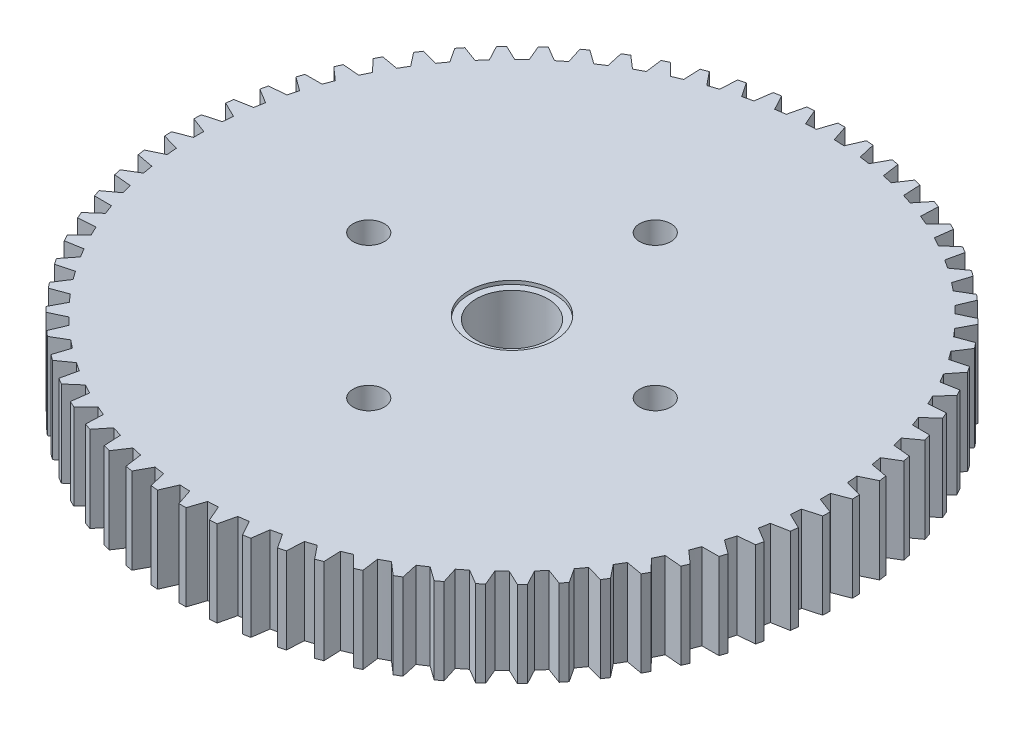
SolidWorks part; units mm, degrees
material "ABS"
ref_plane "Front" through (0, 0, 0) normal (0, 0, 1) x (1, 0, 0)
ref_plane "Top" through (0, 0, 0) normal (0, 1, 0) x (1, 0, 0)
ref_plane "Right" through (0, 0, 0) normal (1, 0, 0) x (0, 0, -1)
sketch "Sketch2" plane through (0, 0, 0) normal (0, 1, 0) x (1, 0, 0)
  circle A0 centre (0, 0) radius 21.875
  circle A1 centre (0, 0) radius 2.5
  dimension "D1" = 43.75
  dimension "D2" = 5
extrude "Boss-Extrude1" add sketch "Sketch2" along normal blind 6
ref_plane "Plane1" through (0, 3.5, 0) normal (0, 1, 0) x (1, 0, 0)
sketch "Sketch3" plane through (0, 3.5, 0) normal (0, 1, 0) x (1, 0, 0)
  line L0 (0, 21.875) -> (0, -21.875) construction
  line L1 (-21.875, 0) -> (21.875, 0) construction
  line L3 (0, 21.875) -> (0, 23) construction
  line L4 (-0.625, 21.8661) -> (-0.25, 23)
  line L5 (-0.25, 23) -> (0.25, 23)
  line L6 (0.625, 21.8661) -> (0.25, 23)
  circle A0 centre (0, 0) radius 21.875 construction
  arc A1 (-21.875, 0) -> (21.875, 0) centre (0, 0) ccw
  arc A2 (0.625, 21.8661) -> (-0.625, 21.8661) centre (0, 0) ccw
  dimension "D1" = 1.25
  dimension "D2" = 0.25
  dimension "D3" = 23
extrude "Boss-Extrude2" add sketch "Sketch3" along normal blind 2.5 and the other way blind 3.5 contours L6 L5 L4 A2
pattern_circular "CirPattern1" count 70 over 360 about axis through (0, 6, 0) along (0, 1, 0) of "Boss-Extrude2"
sketch "Sketch4" plane through (0, 6, 0) normal (0, 1, 0) x (1, 0, 0)
  circle A0 centre (0, 0) radius 3
  circle A1 centre (0, 0) radius 2.5
  circle A2 centre (0, 0) radius 2.5 construction
  dimension "D1" = 0.5
extrude "Cut-Extrude1" cut sketch "Sketch4" against normal blind 0.25
ref_plane "Plane2" through (0, 6, 0) normal (0, 1, 0) x (1, 0, 0)
sketch "Sketch5" plane through (0, 6, 0) normal (0, 1, 0) x (1, 0, 0)
  line L0 (-34.259, 0) -> (34.259, 0) construction
  line L1 (0, -34.259) -> (0, 34.259) construction
  circle A0 centre (0, 10) radius 1.09
  point P6 (0, 0)
  dimension "D1" = 10
  dimension "D2" = 2.18
extrude "Cut-Extrude2" cut sketch "Sketch5" against normal up to surface (6 mm away) up to face at (0, 0, 0)
pattern_circular "CirPattern2" count 4 over 360 about axis through (0, 5.75, 0) along (0, 1, 0) of "Cut-Extrude2"
sketch "Sketch6" plane through (0, 0, 0) normal (0, -1, 0) x (-1, 0, 0)
  circle A0 centre (0, 0) radius 3.15
  circle A1 centre (0, 0) radius 2.8
  dimension "D1" = 6.3
  dimension "D2" = 5.6
extrude "Boss-Extrude3" add sketch "Sketch6" along normal blind 3
